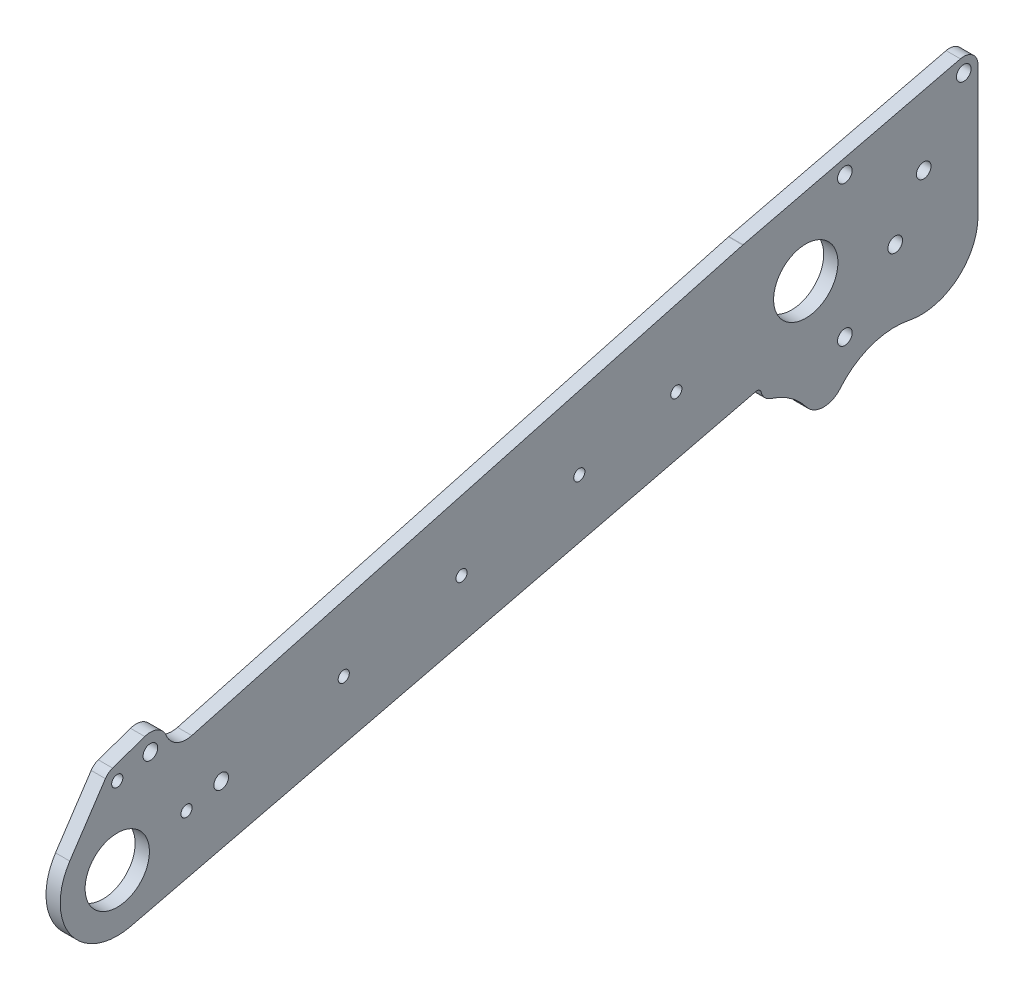
SolidWorks part; units mm, degrees
ref_plane "Alzado" through (0, 0, 0) normal (0, 0, 1) x (1, 0, 0)
ref_plane "Planta" through (0, 0, 0) normal (0, 1, 0) x (1, 0, 0)
ref_plane "Vista lateral" through (0, 0, 0) normal (1, 0, 0) x (0, 0, -1)
sketch "Croquis1" plane through (0, 0, 0) normal (0, 1, 0) x (1, 0, 0)
  line L1 (-101.6, -12.7) -> (101.6, -12.7)
  line L2 (-101.6, -12.7) -> (-101.6, 12.7)
  line L3 (-101.6, 12.7) -> (101.6, 12.7)
  line L4 (101.6, -12.7) -> (101.6, 12.7)
  line L5 (-101.6, -12.7) -> (101.6, 12.7) construction
  line L6 (-101.6, 12.7) -> (101.6, -12.7) construction
  point P0 (0, 0)
  dimension "D1" = 25.4
  dimension "D2" = 203.2
extrude "Saliente-Extruir1" add sketch "Croquis1" along normal blind 25.4
shell "Vaciado1" thickness 3.175 removed face at (-101.6, 12.7, 0) removed face at (101.6, 12.7, 0)
sketch "Croquis2" plane through (0, 25.4, 0) normal (0, 1, 0) x (1, 0, 0)
  line L0 (101.6, 12.7) -> (-101.6, 12.7) construction
  line L1 (-25.4, -12.7) -> (25.4, -12.7)
  line L2 (-25.4, -12.7) -> (-25.4, 12.7)
  line L3 (-25.4, 12.7) -> (25.4, 12.7)
  line L4 (25.4, -12.7) -> (25.4, 12.7)
  line L5 (-25.4, -12.7) -> (25.4, 12.7) construction
  line L6 (-25.4, 12.7) -> (25.4, -12.7) construction
  line L8 (-22.225, -9.525) -> (22.225, -9.525)
  line L9 (-22.225, -9.525) -> (-22.225, 9.525)
  line L10 (-22.225, 9.525) -> (22.225, 9.525)
  line L11 (22.225, -9.525) -> (22.225, 9.525)
  line L12 (-22.225, -9.525) -> (22.225, 9.525) construction
  line L13 (-22.225, 9.525) -> (22.225, -9.525) construction
  point P0 (0, 0)
  point P8 (0, 0)
  dimension "D1" = 50.8
  dimension "D2" = 3.175
  dimension "D3" = 3.175
extrude "Saliente-Extruir2" add sketch "Croquis2" along normal blind 247.65 separate body
sketch "Croquis3" plane through (0, 25.4, 0) normal (0, 1, 0) x (1, 0, 0)
  line L0 (0, 0) -> (0, 12.7) construction
  line L1 (25.4, 12.7) -> (-25.4, 12.7) construction
  circle A0 centre (-47.625, 0) radius 3.2639
  circle A1 centre (-79.375, 0) radius 3.2639
  circle A2 centre (79.375, 0) radius 3.2639
  circle A3 centre (47.625, 0) radius 3.2639
  dimension "D1" = 47.625
  dimension "D2" = 6.5278
  dimension "D3" = 31.75
extrude "Cortar-Extruir1" cut sketch "Croquis3" against normal through all
sketch "Croquis4" plane through (0, 0, 12.7) normal (0, 0, 1) x (1, 0, 0)
  line L0 (0, 25.4) -> (0, 139.6619) construction
  line L1 (-101.6, 25.4) -> (101.6, 25.4) construction
  line L2 (0, 139.6619) -> (-23.8125, 139.6619) construction
  circle A0 centre (0, 139.6619) radius 14.3129
  circle A1 centre (0, 139.6619) radius 23.8125 construction
  circle A2 centre (-23.8125, 139.6619) radius 2.4892 construction
  circle A3 centre (-11.9062, 160.2841) radius 2.4892
  circle A4 centre (11.9063, 160.2841) radius 2.4892
  circle A5 centre (23.8125, 139.6619) radius 2.4892 construction
  circle A6 centre (11.9062, 119.0397) radius 2.4892
  circle A7 centre (-11.9063, 119.0397) radius 2.4892
  dimension "D1" = 28.6258
  dimension "D3" = 47.625
  dimension "D4" = 4.9784
  dimension "D2" = 114.2619
  dimension "D6" = 23.8125
  dimension "D5" = 6
extrude "Cortar-Extruir2" cut sketch "Croquis4" against normal through all
sketch "Croquis8" plane through (0, 0, 12.7) normal (0, 0, 1) x (1, 0, 0)
  line L0 (0, 0) -> (0, 273.05) construction
  line L1 (-101.6, 12.7) -> (0, 12.7) construction
  line L2 (-101.6, 25.4) -> (-101.6, 0) construction
  line L3 (0, 12.7) -> (-12.7, 12.7) construction
  line L4 (0, 12.7) -> (12.7, 12.7) construction
  line L5 (-25.4, 273.05) -> (25.4, 273.05) construction
  line L6 (-12.7, 12.7) -> (-12.7, 25.4) construction
  circle A0 centre (0, 12.7) radius 2.4892
  circle A1 centre (-12.7, 12.7) radius 2.4892
  circle A2 centre (-25.4, 12.7) radius 2.4892
  circle A3 centre (-38.1, 12.7) radius 2.4892
  circle A4 centre (-50.8, 12.7) radius 2.4892
  circle A5 centre (0, 12.7) radius 2.4892
  circle A6 centre (-12.7, 12.7) radius 2.4892
  circle A7 centre (-25.4, 12.7) radius 2.4892
  circle A8 centre (-38.1, 12.7) radius 2.4892
  circle A9 centre (12.7, 12.7) radius 2.4892
  circle A10 centre (0, 12.7) radius 2.4892
  circle A11 centre (-12.7, 12.7) radius 2.4892
  circle A12 centre (-25.4, 12.7) radius 2.4892
  circle A13 centre (25.4, 12.7) radius 2.4892
  circle A14 centre (12.7, 12.7) radius 2.4892
  circle A15 centre (0, 12.7) radius 2.4892
  circle A16 centre (-12.7, 12.7) radius 2.4892
  circle A17 centre (38.1, 12.7) radius 2.4892
  circle A18 centre (25.4, 12.7) radius 2.4892
  circle A19 centre (12.7, 12.7) radius 2.4892
  circle A20 centre (0, 12.7) radius 2.4892
  circle A21 centre (12.7, 12.7) radius 2.4892
  circle A22 centre (25.4, 12.7) radius 2.4892
  circle A23 centre (38.1, 12.7) radius 2.4892
  circle A24 centre (50.8, 12.7) radius 2.4892
  circle A25 centre (-12.7, 25.4) radius 2.4892 [skipped]
  circle A26 centre (12.7, 25.4) radius 2.4892 [skipped]
  circle A27 centre (-12.7, 38.1) radius 2.4892
  circle A28 centre (12.7, 38.1) radius 2.4892
  circle A29 centre (-12.7, 50.8) radius 2.4892
  circle A30 centre (12.7, 50.8) radius 2.4892
  circle A31 centre (-12.7, 63.5) radius 2.4892
  circle A32 centre (12.7, 63.5) radius 2.4892
  circle A33 centre (-12.7, 76.2) radius 2.4892
  circle A34 centre (12.7, 76.2) radius 2.4892
  dimension "D1" = 4.9784
  dimension "D4" = 12.7
  dimension "D5" = 12.7
  dimension "D7" = 12.7
  dimension "D2" = 5
  dimension "D3" = 5
  dimension "D6" = 6
extrude "Cortar-Extruir4" cut sketch "Croquis8" against normal through all contours A4 | A3 | A2 | A1 | A0 | A9 | A13 | A17 | A24 | A28 | A29 | A30 | A31 | A32 | A34 | A33 | A27 region at (0, 12.7, 12.7) region at (-12.7, 12.7, 12.7) region at (-25.4, 12.7, 12.7) region at (-38.1, 12.7, 12.7) region at (-50.8, 12.7, 12.7) region at (12.7, 12.7, 12.7) region at (25.4, 12.7, 12.7) region at (38.1, 12.7, 12.7) region at (50.8, 12.7, 12.7) region at (12.7, 38.1, 12.7) region at (-12.7, 50.8, 12.7) region at (12.7, 50.8, 12.7) region at (-12.7, 63.5, 12.7) region at (12.7, 63.5, 12.7) region at (-12.7, 76.2, 12.7) region at (12.7, 76.2, 12.7)
sketch "Croquis6" plane through (0, 0, 12.7) normal (0, 0, 1) x (1, 0, 0)
  line L0 (25.4, 273.05) -> (25.4, 25.4) construction
  line L1 (-25.4, 88.646) -> (25.4, 88.646)
  line L2 (-25.4, 88.646) -> (-25.4, 114.046)
  line L3 (-25.4, 114.046) -> (25.4, 114.046)
  line L4 (25.4, 88.646) -> (25.4, 114.046)
  line L5 (-25.4, 88.646) -> (25.4, 114.046) construction
  line L6 (-25.4, 114.046) -> (25.4, 88.646) construction
  line L7 (-101.6, 25.4) -> (101.6, 25.4) construction
  line L9 (-22.225, 91.821) -> (22.225, 91.821)
  line L10 (-22.225, 91.821) -> (-22.225, 110.871)
  line L11 (-22.225, 110.871) -> (22.225, 110.871)
  line L12 (22.225, 91.821) -> (22.225, 110.871)
  line L13 (-22.225, 91.821) -> (22.225, 110.871) construction
  line L14 (-22.225, 110.871) -> (22.225, 91.821) construction
  point P0 (0, 101.346)
  point P11 (0, 101.346)
  dimension "D1" = 25.4
  dimension "D2" = 63.246
  dimension "D3" = 3.175
  dimension "D4" = 3.175
extrude "Saliente-Extruir3" add sketch "Croquis6" along normal blind 69.85 separate body
sketch "Croquis7" plane through (0, 114.046, 0) normal (0, 1, 0) x (1, 0, 0)
  line L0 (0, -12.7) -> (0, -82.55) construction
  line L1 (-25.4, -12.7) -> (25.4, -12.7) construction
  line L2 (25.4, -82.55) -> (-25.4, -82.55) construction
  line L3 (16.51, -12.7) -> (-16.51, -12.7)
  line L4 (25.4, -12.7) -> (-25.4, -12.7) construction
  line L5 (-16.51, -12.7) -> (-16.51, -34.798)
  line L6 (-13.208, -38.1) -> (13.208, -38.1)
  line L7 (16.51, -12.7) -> (16.51, -34.798)
  arc A0 (16.51, -34.798) -> (13.208, -38.1) centre (13.208, -34.798) cw
  arc A1 (-16.51, -34.798) -> (-13.208, -38.1) centre (-13.208, -34.798) ccw
  point P12 (0, -38.1)
  point P16 (16.51, -38.1)
  point P19 (-16.51, -38.1)
  dimension "D3" = 3.302
  dimension "D1" = 25.4
  dimension "D2" = 33.02
extrude "Cortar-Extruir3" cut sketch "Croquis7" against normal up to next (3.175 mm away)
sketch "Croquis11" plane through (25.4, 0, 0) normal (1, 0, 0) x (0, 0, -1)
  line L0 (0, -101.854) -> (-381, -101.854) construction
  line L1 (-82.55, 88.646) -> (-82.55, 114.046) construction
  line L2 (-82.55, 88.646) -> (-12.7, 88.646) construction
  line L6 (-517.96, -101.854) -> (-276.66, -101.854) construction
  line L7 (-517.96, -101.854) -> (-517.96, 139.446) construction
  line L8 (-517.96, 139.446) -> (-276.66, 139.446) construction
  line L9 (-276.66, -101.854) -> (-276.66, 139.446) construction
  circle A0 centre (-396.875, 145.796) radius 38.1
  dimension "D3" = 76.2
  dimension "D4" = 209.55
  dimension "D5" = 276.225
  dimension "D1" = 190.5
  dimension "D2" = 381
  dimension "D6" = 241.3
sketch "Croquis9" plane through (0, 0, 12.7) normal (0, 0, 1) x (1, 0, 0)
  line L0 (0, 0) -> (0, 273.05) construction
  line L1 (-25.4, 273.05) -> (25.4, 273.05) construction
  line L2 (50.8, 0) -> (-50.8, 0)
  line L3 (-101.6, 0) -> (101.6, 0) construction
  line L4 (-57.15, 6.35) -> (-57.15, 23.7481)
  line L5 (-101.6, 25.4) -> (101.6, 25.4) construction
  line L6 (-56.3451, 26.8425) -> (-27.2168, 79.0403)
  line L7 (-25.4, 273.05) -> (-25.4, 25.4) construction
  line L8 (-21.6717, 82.296) -> (21.6717, 82.296)
  line L9 (56.3451, 26.8425) -> (27.2168, 79.0403)
  line L10 (57.15, 6.35) -> (57.15, 23.7481)
  line L11 (-25.4, 88.646) -> (25.4, 88.646) construction
  circle A0 centre (-50.8, 12.7) radius 2.4892 construction
  arc A2 (-50.8, 0) -> (-57.15, 6.35) centre (-50.8, 6.35) cw
  arc A3 (-57.15, 23.7481) -> (-56.3451, 26.8425) centre (-50.8, 23.7481) cw
  arc A4 (-27.2168, 79.0403) -> (-21.6717, 82.296) centre (-21.6717, 75.946) cw
  arc A5 (27.2168, 79.0403) -> (21.6717, 82.296) centre (21.6717, 75.946) ccw
  arc A6 (57.15, 23.7481) -> (56.3451, 26.8425) centre (50.8, 23.7481) ccw
  arc A7 (50.8, 0) -> (57.15, 6.35) centre (50.8, 6.35) ccw
  circle A9 centre (-25.4, 12.7) radius 2.4892
  circle A10 centre (-25.4, 12.7) radius 2.4892
  circle A11 centre (-12.7, 12.7) radius 2.4892
  circle A12 centre (-12.7, 12.7) radius 2.4892
  circle A13 centre (0, 12.7) radius 2.4892
  circle A14 centre (0, 12.7) radius 2.4892
  circle A15 centre (0, 12.7) radius 2.4892
  circle A16 centre (0, 12.7) radius 2.4892
  circle A17 centre (12.7, 12.7) radius 2.4892
  circle A18 centre (12.7, 12.7) radius 2.4892
  circle A19 centre (-38.1, 12.7) radius 2.4892
  circle A20 centre (-38.1, 12.7) radius 2.4892
  circle A21 centre (-25.4, 12.7) radius 2.4892
  circle A22 centre (-25.4, 12.7) radius 2.4892
  circle A23 centre (-12.7, 12.7) radius 2.4892
  circle A24 centre (-12.7, 12.7) radius 2.4892
  circle A25 centre (0, 12.7) radius 2.4892
  circle A26 centre (0, 12.7) radius 2.4892
  circle A27 centre (-50.8, 12.7) radius 2.4892
  circle A28 centre (-50.8, 12.7) radius 2.4892
  circle A29 centre (-38.1, 12.7) radius 2.4892
  circle A30 centre (-38.1, 12.7) radius 2.4892
  circle A31 centre (25.4, 12.7) radius 2.4892
  circle A32 centre (25.4, 12.7) radius 2.4892
  circle A33 centre (38.1, 12.7) radius 2.4892
  circle A34 centre (38.1, 12.7) radius 2.4892
  circle A35 centre (-12.7, 12.7) radius 2.4892
  circle A36 centre (-12.7, 12.7) radius 2.4892
  circle A37 centre (0, 12.7) radius 2.4892
  circle A38 centre (0, 12.7) radius 2.4892
  circle A39 centre (12.7, 12.7) radius 2.4892
  circle A40 centre (12.7, 12.7) radius 2.4892
  circle A41 centre (25.4, 12.7) radius 2.4892
  circle A42 centre (25.4, 12.7) radius 2.4892
  circle A43 centre (-25.4, 12.7) radius 2.4892
  circle A44 centre (-25.4, 12.7) radius 2.4892
  circle A45 centre (-12.7, 12.7) radius 2.4892
  circle A46 centre (-12.7, 12.7) radius 2.4892
  circle A47 centre (50.8, 12.7) radius 2.4892
  circle A48 centre (50.8, 12.7) radius 2.4892
  circle A49 centre (38.1, 12.7) radius 2.4892
  circle A50 centre (38.1, 12.7) radius 2.4892
  circle A51 centre (25.4, 12.7) radius 2.4892
  circle A52 centre (25.4, 12.7) radius 2.4892
  circle A53 centre (12.7, 12.7) radius 2.4892
  circle A54 centre (12.7, 12.7) radius 2.4892
  circle A55 centre (0, 12.7) radius 2.4892
  circle A56 centre (0, 12.7) radius 2.4892
  circle A57 centre (12.7, 12.7) radius 2.4892
  circle A58 centre (12.7, 12.7) radius 2.4892
  circle A59 centre (-12.7, 76.2) radius 2.4892
  circle A60 centre (-12.7, 76.2) radius 2.4892
  circle A61 centre (12.7, 63.5) radius 2.4892
  circle A62 centre (12.7, 63.5) radius 2.4892
  circle A63 centre (-12.7, 63.5) radius 2.4892
  circle A64 centre (-12.7, 63.5) radius 2.4892
  circle A65 centre (12.7, 50.8) radius 2.4892
  circle A66 centre (12.7, 50.8) radius 2.4892
  circle A67 centre (-12.7, 50.8) radius 2.4892
  circle A68 centre (-12.7, 50.8) radius 2.4892
  circle A69 centre (12.7, 38.1) radius 2.4892
  circle A70 centre (12.7, 38.1) radius 2.4892
  circle A71 centre (-12.7, 38.1) radius 2.4892
  circle A72 centre (-12.7, 38.1) radius 2.4892
  circle A73 centre (12.7, 76.2) radius 2.4892
  circle A74 centre (12.7, 76.2) radius 2.4892
  point P22 (-57.15, 0)
  point P25 (-57.15, 25.4)
  point P28 (-25.4, 82.296)
  point P38 (0, 82.296)
  dimension "D1" = 6.35
  dimension "D3" = 6.35
  dimension "D37" = 6.35
  dimension "D4" = 0
  dimension "D5" = 0
  dimension "D6" = 0
  dimension "D7" = 0
  dimension "D8" = 0
  dimension "D9" = 0
  dimension "D10" = 0
  dimension "D11" = 0
  dimension "D12" = 0
  dimension "D13" = 0
  dimension "D14" = 0
  dimension "D15" = 0
  dimension "D16" = 0
  dimension "D17" = 0
  dimension "D18" = 0
  dimension "D19" = 0
  dimension "D20" = 0
  dimension "D21" = 0
  dimension "D22" = 0
  dimension "D23" = 0
  dimension "D24" = 0
  dimension "D25" = 0
  dimension "D26" = 0
  dimension "D27" = 0
  dimension "D28" = 0
  dimension "D29" = 0
  dimension "D30" = 0
  dimension "D31" = 0
  dimension "D32" = 0
  dimension "D33" = 0
  dimension "D34" = 0
  dimension "D35" = 0
  dimension "D36" = 0
extrude "Saliente-Extruir4" add sketch "Croquis9" along normal blind 6.35 separate body contours L0 L8 A4 L6 A3 A60 A64 A68 A72 | L0 A6 L9 A5 L8 A74 A70 A66 A62 | L0 A3 L4 A2 | L0 L2 A7 L10 A6 A56 region at (-24.3725, 36.0328, 12.7) region at (24.3725, 36.0328, 12.7)
sketch "Croquis15" plane through (25.4, 0, 0) normal (1, 0, 0) x (0, 0, -1)
  line L0 (-12.7, 0) -> (-12.7, 171.1325) construction
  line L1 (-12.7, 273.05) -> (-12.7, 25.4) construction
  line L2 (-72.5746, 227.1642) -> (-41.5317, 154.1315) construction
  line L3 (-105.4538, 208.2656) -> (-57.9713, 144.6822) construction
  line L4 (-94.6246, 238.2605) -> (-401.3483, 164.3633) construction
  line L5 (-392.4017, 127.2287) -> (-85.6779, 201.1258) construction
  line L8 (-82.55, 114.046) -> (-12.7, 114.046) construction
  circle A0 centre (-50.32, 150.396) radius 30
  arc A1 (-57.9713, 144.6822) -> (-41.5317, 154.1315) centre (-50.32, 150.396) ccw construction
  arc A2 (-401.3483, 164.3633) -> (-392.4017, 127.2287) centre (-396.875, 145.796) ccw construction
  arc A3 (-72.5746, 227.1642) -> (-105.4538, 208.2656) centre (-90.1513, 219.6932) ccw construction
  arc A4 (-85.6779, 201.1258) -> (-94.6246, 238.2605) centre (-90.1513, 219.6932) ccw construction
  dimension "D2" = 60
  dimension "D3" = 19.0986
  dimension "D4" = 38.1972
  dimension "D1" = 171.1325
  dimension "D7" = 6.35
  dimension "D8" = 7.62
sketch "Croquis16" plane through (25.4, 0, 0) normal (1, 0, 0) x (0, 0, -1)
  line L0 (-50.32, 150.396) -> (-50.32, 175.796) construction
  line L1 (-13.4332, 272.8734) -> (-118.1525, 247.644)
  line L2 (-82.55, 94.996) -> (-82.55, 113.9625)
  line L3 (-82.5522, 114.1295) -> (-83.4835, 149.5234)
  line L4 (-76.2, 88.646) -> (6.35, 88.646)
  line L5 (12.7, 273.05) -> (12.7, 25.4) construction
  line L6 (12.7, 94.996) -> (12.7, 266.7)
  line L7 (6.35, 273.05) -> (-11.9459, 273.05)
  line L8 (-94.6246, 238.2605) -> (-401.3483, 164.3633) construction
  line L9 (-122.8385, 239.9833) -> (-110.0117, 186.743)
  line L10 (-90.1513, 219.6932) -> (-116.4251, 213.3632) construction
  circle A0 centre (-90.1513, 219.6932) radius 14.3256
  circle A1 centre (-50.32, 150.396) radius 33.175
  circle A4 centre (-50.32, 150.396) radius 9.5631
  circle A5 centre (-50.32, 150.396) radius 25.4 construction
  circle A6 centre (-50.32, 175.796) radius 2.4892
  circle A7 centre (-32.3595, 168.3565) radius 2.4892 construction
  circle A8 centre (-24.92, 150.396) radius 2.4892
  circle A9 centre (-32.3595, 132.4355) radius 2.4892
  circle A10 centre (-50.32, 124.996) radius 2.4892
  circle A11 centre (-68.2805, 132.4355) radius 2.4892
  circle A12 centre (-75.72, 150.396) radius 2.4892
  circle A13 centre (-68.2805, 168.3565) radius 2.4892
  arc A18 (-105.7366, 182.1707) -> (-83.4864, 151.1506) centre (-115.2282, 151.8727) cw
  arc A19 (-110.0117, 186.743) -> (-105.7366, 182.1707) centre (-103.8383, 188.2304) ccw
  arc A21 (-118.1525, 247.644) -> (-122.8385, 239.9833) centre (-116.6652, 241.4706) ccw
  arc A23 (-11.9459, 273.05) -> (-13.4332, 272.8734) centre (-11.9459, 266.7) ccw
  circle A26 centre (-50.32, 150.396) radius 30 construction
  arc A29 (-82.55, 113.9625) -> (-82.5522, 114.1295) centre (-88.9, 113.9625) ccw
  arc A31 (12.7, 266.7) -> (6.35, 273.05) centre (6.35, 266.7) ccw
  arc A32 (6.35, 88.646) -> (12.7, 94.996) centre (6.35, 94.996) ccw
  arc A33 (-82.55, 94.996) -> (-76.2, 88.646) centre (-76.2, 94.996) ccw
  point P45 (-12.7, 273.05)
  point P72 (-82.55, 114.046)
  point P74 (12.7, 273.05)
  point P77 (12.7, 88.646)
  point P80 (-82.55, 88.646)
  dimension "D1" = 28.6512
  dimension "D2" = 3.175
  dimension "D3" = 31.75
  dimension "D4" = 19.1262
  dimension "D5" = 50.8
  dimension "D6" = 4.9784
  dimension "D9" = 6.35
  dimension "D10" = 6.35
  dimension "D14" = 6.35
  dimension "D15" = 6.35
  dimension "D12" = 6.35
  dimension "D8" = 25.4
  dimension "D11" = 12.7
  dimension "D7" = 8
extrude "Saliente-Extruir5" add sketch "Croquis16" along normal blind 6.35 separate body contours L4 A32 A31 A23 | L2 A33 L4 A23 L1 A21 L9 A19 A18 A1 L3 A29 A0 | A1 A13 A12 A11 A10 A9 A8 A6 A4 region at (25.4, 188.5949, 38.9873) region at (25.4, 182.6306, 49.9534)
sketch "Croquis12" plane through (25.4, 0, 0) normal (1, 0, 0) x (0, 0, -1)
  line L0 (-82.55, 101.346) -> (-12.7, 101.346) construction
  line L1 (-82.55, 88.646) -> (-82.55, 114.046) construction
  line L2 (-12.7, 88.646) -> (-12.7, 114.046) construction
  line L3 (0, 273.05) -> (0, 0) construction
  line L4 (-12.7, 273.05) -> (12.7, 273.05) construction
  line L5 (0, 101.346) -> (-12.7, 101.346) construction
  line L6 (0, 101.346) -> (0, 114.046) construction
  circle A1 centre (0, 101.346) radius 2.4892
  circle A2 centre (-12.7, 101.346) radius 2.4892 [skipped]
  circle A3 centre (-25.4, 101.346) radius 2.4892
  circle A4 centre (-38.1, 101.346) radius 2.4892
  circle A5 centre (-50.8, 101.346) radius 2.4892
  circle A6 centre (0, 114.046) radius 2.4892
  circle A7 centre (0, 126.746) radius 2.4892
  circle A8 centre (0, 139.446) radius 2.4892
  circle A9 centre (0, 152.146) radius 2.4892
  circle A10 centre (0, 164.846) radius 2.4892
  circle A11 centre (0, 177.546) radius 2.4892
  circle A12 centre (0, 190.246) radius 2.4892
  circle A13 centre (0, 202.946) radius 2.4892
  circle A14 centre (0, 215.646) radius 2.4892
  circle A15 centre (0, 228.346) radius 2.4892
  circle A16 centre (0, 241.046) radius 2.4892
  circle A17 centre (0, 253.746) radius 2.4892
  circle A18 centre (0, 266.446) radius 2.4892
  circle A19 centre (-63.5, 101.346) radius 2.4892
  circle A20 centre (-76.2, 101.346) radius 2.4892
  dimension "D1" = 4.9784
  dimension "D3" = 12.7
  dimension "D5" = 12.7
  dimension "D2" = 7
  dimension "D4" = 14
extrude "Cortar-Extruir5" cut sketch "Croquis12" against normal through all and the other way through all
sketch "Croquis17" plane through (31.75, 0, 0) normal (1, 0, 0) x (0, 0, -1)
  line L0 (-403.5186, 170.3118) -> (-118.2389, 247.6205)
  line L1 (-118.0654, 247.6649) -> (-21.2705, 270.9852)
  line L2 (-390.9258, 121.1026) -> (-118.1525, 186.8202)
  line L3 (-392.4017, 127.2287) -> (-85.6779, 201.1258) construction
  line L4 (-118.1525, 186.8202) -> (-112.4025, 188.2055)
  line L5 (-13.4332, 206.3797) -> (-13.4332, 264.8118)
  line L6 (-398.9636, 186.2074) -> (-384.6217, 191.2027)
  line L7 (-402.1634, 183.7258) -> (-418.0287, 159.8559)
  circle A0 centre (-396.875, 145.796) radius 14.3256
  circle A1 centre (-90.1513, 219.6932) radius 14.3256
  circle A2 centre (-396.875, 145.796) radius 25.4
  arc A3 (-118.2389, 247.6205) -> (-118.0654, 247.6649) centre (-116.578, 241.4916) cw
  arc A4 (-21.2705, 270.9852) -> (-13.4332, 264.8118) centre (-19.7832, 264.8118) cw
  arc A5 (-13.4332, 206.3797) -> (-43.9384, 181.4981) centre (-38.8332, 206.3797) cw
  circle A6 centre (-50.32, 150.396) radius 31.75
  arc A8 (-110.0117, 186.743) -> (-105.7366, 182.1707) centre (-103.8383, 188.2304) ccw construction
  arc A9 (-110.0117, 186.743) -> (-105.7366, 182.1707) centre (-103.8383, 188.2304) ccw
  arc A10 (-110.0117, 186.743) -> (-112.4025, 188.2055) centre (-111.9383, 186.2789) ccw
  arc A11 (-83.4864, 151.1506) -> (-105.7366, 182.1707) centre (-115.2282, 151.8727) ccw construction
  arc A12 (-89.8175, 170.9084) -> (-105.7366, 182.1707) centre (-115.2282, 151.8727) ccw
  arc A13 (-89.8175, 170.9084) -> (-74.8387, 170.5677) centre (-82.1943, 176.6192) ccw
  circle A14 centre (-396.875, 180.2108) radius 6.35
  circle A15 centre (-382.1153, 184.0067) radius 7.62
  arc A17 (-375.0276, 186.8047) -> (-363.6766, 181.1087) centre (-366.1679, 190.3021) ccw
  point P19 (-118.1525, 247.644)
  point P23 (-13.4332, 272.8734)
  line M28 (-13.4332, 272.8734) -> (-118.1525, 247.644)
  arc M29 (-118.1525, 247.644) -> (-122.8385, 239.9833) centre (-116.6652, 241.4706) ccw
  line M30 (-122.8385, 239.9833) -> (-110.0117, 186.743)
  circle M38 centre (-90.1513, 219.6932) radius 14.3256
  dimension "D1" = 28.6512
  dimension "D2" = 50.8
  dimension "D3" = 6.35
  dimension "D4" = 63.5
  dimension "D5" = 9.525
  dimension "D6" = 25.4
  dimension "D7" = 12.7
  dimension "D8" = 34.4148
  dimension "D9" = 15.24
  dimension "D10" = 15.24
  dimension "D11" = 9.525
extrude "Saliente-Extruir6" add sketch "Croquis17" along normal blind 6.35 separate body contours A2 L2 L0 M30 M29 | L5 A4 A3 L0 M28 M29 M30 M38 | A2 A0 | A14 L7 A2 L0 | A14 | A15 | A17 A15 L0 region at (31.75, 166.8023, 412.0119) region at (31.75, 184.8147, 244.5216) region at (31.75, 165.3985, 381.8776) region at (31.75, 180.6264, 372.6967) region at (31.75, 184.0067, 382.1153) region at (31.75, 180.2108, 396.875) region at (31.75, 220.7032, 61.6214)
sketch "Croquis18" plane through (38.1, 0, 0) normal (1, 0, 0) x (0, 0, -1)
  line L0 (-122.8385, 239.9833) -> (-110.0117, 186.743) construction
  line L1 (-122.754, 239.6323) -> (-111.9631, 194.8431)
  line L2 (-403.5186, 170.3118) -> (-118.2389, 247.6205) construction
  line L3 (-402.1634, 183.7258) -> (-418.0287, 159.8559) construction
  line L4 (-398.9636, 186.2074) -> (-384.6217, 191.2027) construction
  line L5 (-402.1634, 183.7258) -> (-418.0287, 159.8559)
  line L6 (-390.9258, 121.1026) -> (-118.1525, 186.8202) construction
  line L7 (-403.5186, 170.3118) -> (-130.5882, 244.274)
  line L8 (-398.9636, 186.2074) -> (-384.6217, 191.2027)
  line L10 (-122.8385, 239.9833) -> (-110.0117, 186.743) construction
  line L11 (-390.9258, 121.1026) -> (-116.6492, 187.1824)
  circle A1 centre (-396.875, 145.796) radius 25.4
  circle A2 centre (-396.875, 145.796) radius 25.4
  arc A3 (-116.6492, 187.1824) -> (-111.9631, 194.8431) centre (-118.1365, 193.3558) ccw
  circle A5 centre (-396.875, 145.796) radius 14.3256
  circle A6 centre (-396.875, 145.796) radius 14.3256
  arc A12 (-122.754, 239.6323) -> (-130.5882, 244.274) centre (-128.9273, 238.145) ccw
  circle A14 centre (-396.875, 180.2108) radius 6.35 construction
  arc A15 (-375.0276, 186.8047) -> (-363.6766, 181.1087) centre (-366.1679, 190.3021) ccw construction
  circle A16 centre (-396.875, 180.2108) radius 6.35
  arc A17 (-375.0276, 186.8047) -> (-384.6217, 191.2027) centre (-382.1153, 184.0067) ccw construction
  arc A18 (-375.0276, 186.8047) -> (-363.6766, 181.1087) centre (-366.1679, 190.3021) ccw
  arc A19 (-375.0276, 186.8047) -> (-384.6217, 191.2027) centre (-382.1153, 184.0067) ccw
  point P18 (-110.4758, 188.6697)
  line M10 (-118.2389, 247.6205) -> (-363.6766, 181.1087)
  arc M11 (-418.0287, 159.8559) -> (-390.9258, 121.1026) centre (-396.875, 145.796) ccw
  circle M13 centre (-396.875, 145.796) radius 14.3256
  line M33 (-402.1634, 183.7258) -> (-418.0287, 159.8559)
  arc M35 (-398.9636, 186.2074) -> (-402.1634, 183.7258) centre (-396.875, 180.2108) ccw
  dimension "D2" = 6.35
  dimension "D1" = 0
  dimension "D3" = 0
extrude "Saliente-Extruir7" add sketch "Croquis18" along normal blind 6.35 from surface separate body contours L1 A12 A2 A3 M10 | A2 M11 M13 | A16 A2 L7 M33 | A16 M35 region at (38.1, 184.7417, 244.7476) region at (38.1, 180.3032, 388.6206) region at (38.1, 131.6506, 417.1009) region at (38.1, 180.2108, 396.875) starting at face at (25.4, 101.346, -2.4892)
sketch "Croquis22" plane through (38.1, 0, 0) normal (1, 0, 0) x (0, 0, -1)
  line L0 (-396.875, 145.796) -> (-90.1513, 219.6932) construction
  line L1 (-90.1513, 219.6932) -> (-50.32, 150.396) construction
  line L4 (-50.32, 236.121) -> (-37.62, 236.121) construction
  line L5 (-21.2705, 270.9852) -> (-118.0654, 247.6649) construction
  circle A0 centre (-396.875, 180.2108) radius 2.4892
  circle A1 centre (-350.5748, 156.9508) radius 3.2639
  circle A2 centre (-396.875, 145.796) radius 19.0986 construction
  arc A3 (-401.3483, 164.3633) -> (-392.4017, 127.2287) centre (-396.875, 145.796) ccw construction
  circle A4 centre (-350.5748, 156.9508) radius 6.35 construction
  circle A7 centre (-72.747, 189.4137) radius 3.2639
  circle A8 centre (-72.747, 189.4137) radius 6.35 construction
  circle A9 centre (-50.32, 213.896) radius 6.35 construction
  circle A10 centre (-50.32, 213.896) radius 3.2639
  circle A13 centre (-37.62, 236.121) radius 3.2639
  circle A14 centre (-37.62, 236.121) radius 6.35 construction
  circle A15 centre (-72.747, 252.0515) radius 3.2639
  circle A16 centre (-72.747, 252.0515) radius 6.35 construction
  circle A17 centre (-19.7832, 264.8118) radius 6.35 construction
  circle A18 centre (-19.7832, 264.8118) radius 3.2639
  circle A19 centre (-382.1153, 184.0067) radius 3.2639
  circle A20 centre (-366.0082, 153.2326) radius 2.4892
  circle A21 centre (-366.0082, 153.2326) radius 4.7625 construction
  dimension "D1" = 6.5278
  dimension "D2" = 47.625
  dimension "D3" = 12.7
  dimension "D4" = 34.925
  dimension "D5" = 63.5
  dimension "D6" = 22.225
  dimension "D7" = 12.7
  dimension "D8" = 4.9784
  dimension "D9" = 6.5278
  dimension "D10" = 9.525
  dimension "D11" = 31.75
extrude "Cortar-Extruir6" cut sketch "Croquis22" against normal through all
sketch "Croquis24" plane through (38.1, 0, 0) normal (1, 0, 0) x (0, 0, -1)
  line L0 (-396.875, 145.796) -> (-90.1513, 219.6932) construction
  line L1 (-243.5131, 182.7446) -> (-247.9864, 201.3119) construction
  line L2 (-94.6246, 238.2605) -> (-401.3483, 164.3633) construction
  circle A0 centre (-295.9867, 170.1024) radius 2.4892
  circle A1 centre (-191.0395, 195.3867) radius 2.4892
  circle A2 centre (-243.5131, 182.7446) radius 2.4892
  circle A3 centre (-147.826, 205.7979) radius 2.4892
  dimension "D1" = 4.9784
  dimension "D2" = 53.975
  dimension "D3" = 44.45
sketch "Croquis25" plane through (31.75, 0, 0) normal (1, 0, 0) x (0, 0, -1)
  line L0 (-12.7, 0) -> (-12.7, 139.7) construction
  line L1 (-12.7, 123.825) -> (-12.7, 155.575)
  line L2 (-12.7, 0) -> (-12.7, 171.1325) construction
  line L3 (-15.875, 158.75) -> (-17.145, 158.75)
  line L4 (-20.32, 155.575) -> (-20.32, 123.825)
  line L5 (-12.7, 139.7) -> (-20.32, 139.7) construction
  line L6 (-15.875, 120.65) -> (-17.145, 120.65)
  arc A0 (-12.7, 155.575) -> (-15.875, 158.75) centre (-15.875, 155.575) ccw
  arc A1 (-15.875, 120.65) -> (-12.7, 123.825) centre (-15.875, 123.825) ccw
  arc A2 (-17.145, 120.65) -> (-20.32, 123.825) centre (-17.145, 123.825) cw
  arc A3 (-17.145, 158.75) -> (-20.32, 155.575) centre (-17.145, 155.575) ccw
  point P13 (-12.7, 158.75)
  point P16 (-12.7, 120.65)
  point P19 (-20.32, 120.65)
  point P22 (-20.32, 158.75)
  dimension "D4" = 3.175
  dimension "D1" = 139.7
  dimension "D2" = 7.62
  dimension "D3" = 38.1
extrude "Cortar-Extruir8" cut sketch "Croquis25" against normal through all
extrude "Cortar-Extruir9" cut sketch "Croquis24" against normal through all
delete or keep bodies "Sólido-Eliminar/Conservar 1" [suppressed] type keep bodies bodies 112
delete or keep bodies "Sólido-Eliminar/Conservar 2" [suppressed] type keep bodies bodies 111
delete or keep bodies "Sólido-Eliminar/Conservar 3" [suppressed] type keep bodies bodies 107
delete or keep bodies "Sólido-Eliminar/Conservar 4" [suppressed] type keep bodies bodies 109
delete or keep bodies "Sólido-Eliminar/Conservar 5" [suppressed] type keep bodies bodies 121
delete or keep bodies "Sólido-Eliminar/Conservar 6" [suppressed] type keep bodies bodies 125
sketch "Croquis29" [suppressed] plane through (0, 0, 0) normal (1, 0, 0) x (0, 0, -1)
  line L0 (-392.4017, 127.2287) -> (-85.6779, 201.1258) construction
  line L1 (-94.6246, 238.2605) -> (-401.3483, 164.3633) construction
  line L2 (-392.4017, 127.2287) -> (-85.6779, 201.1258) construction
  line L3 (-94.6246, 238.2605) -> (-401.3483, 164.3633) construction
  line L4 (-392.8842, 129.2314) -> (-86.1604, 203.1285)
  line L5 (-94.1421, 236.2578) -> (-400.8658, 162.3606)
  line L6 (-391.9941, 125.5371) -> (-85.2704, 199.4342)
  line L7 (-95.0321, 239.9521) -> (-401.7559, 166.0549)
  arc A0 (-85.6779, 201.1258) -> (-94.6246, 238.2605) centre (-90.1513, 219.6932) ccw construction
  arc A1 (-401.3483, 164.3633) -> (-392.4017, 127.2287) centre (-396.875, 145.796) ccw construction
  arc A2 (-85.6779, 201.1258) -> (-94.6246, 238.2605) centre (-90.1513, 219.6932) ccw construction
  arc A3 (-401.3483, 164.3633) -> (-392.4017, 127.2287) centre (-396.875, 145.796) ccw construction
  arc A4 (-86.1604, 203.1285) -> (-94.1421, 236.2578) centre (-90.1513, 219.6932) ccw
  arc A5 (-400.8658, 162.3606) -> (-392.8842, 129.2314) centre (-396.875, 145.796) ccw
  arc A6 (-401.7559, 166.0549) -> (-391.9941, 125.5371) centre (-396.875, 145.796) ccw
  arc A7 (-85.2704, 199.4342) -> (-95.0321, 239.9521) centre (-90.1513, 219.6932) ccw
  dimension "D1" = 2.06
  dimension "D2" = 3.8
extrude "Saliente-Extruir9" [suppressed] add sketch "Croquis29" along normal mid plane 9 separate body
sketch "Croquis30" [suppressed] plane through (0, 0, 0) normal (1, 0, 0) x (0, 0, -1)
  line L0 (-72.5746, 227.1642) -> (-41.5317, 154.1315) construction
  line L1 (-105.4538, 208.2656) -> (-57.9713, 144.6822) construction
  line L2 (-72.5746, 227.1642) -> (-41.5317, 154.1315) construction
  line L3 (-105.4538, 208.2656) -> (-57.9713, 144.6822) construction
  line L4 (-74.4704, 226.3584) -> (-43.4275, 153.3257)
  line L5 (-103.8032, 209.4982) -> (-56.3207, 145.9148)
  line L6 (-106.8479, 207.2245) -> (-59.3654, 143.6411)
  line L7 (-70.9732, 227.8449) -> (-39.9303, 154.8122)
  arc A0 (-57.9713, 144.6822) -> (-41.5317, 154.1315) centre (-50.32, 150.396) ccw construction
  arc A1 (-72.5746, 227.1642) -> (-105.4538, 208.2656) centre (-90.1513, 219.6932) ccw construction
  arc A2 (-57.9713, 144.6822) -> (-41.5317, 154.1315) centre (-50.32, 150.396) ccw construction
  arc A3 (-72.5746, 227.1642) -> (-105.4538, 208.2656) centre (-90.1513, 219.6932) ccw construction
  arc A4 (-56.3207, 145.9148) -> (-43.4275, 153.3257) centre (-50.32, 150.396) ccw
  arc A5 (-74.4704, 226.3584) -> (-103.8032, 209.4982) centre (-90.1513, 219.6932) ccw
  arc A6 (-70.9732, 227.8449) -> (-106.8479, 207.2245) centre (-90.1513, 219.6932) ccw
  arc A7 (-59.3654, 143.6411) -> (-39.9303, 154.8122) centre (-50.32, 150.396) ccw
  dimension "D1" = 2.06
  dimension "D2" = 3.8
extrude "Saliente-Extruir10" [suppressed] add sketch "Croquis30" along normal mid plane 15 separate body
delete or keep bodies "Sólido-Eliminar/Conservar 7" [suppressed] type keep bodies bodies 123
delete or keep bodies "Sólido-Eliminar/Conservar 8" [suppressed] type keep bodies bodies 124
sketch "Croquis31" [suppressed] plane through (31.75, 0, 0) normal (1, 0, 0) x (0, 0, -1)
  line L0 (-402.1634, 183.7258) -> (-418.0287, 159.8559) construction
  line L1 (-402.1634, 183.7258) -> (-418.0287, 159.8559)
  line L2 (-361.1143, 149.1863) -> (-377.2995, 129.6108)
  circle A0 centre (-396.875, 180.2108) radius 6.35
  circle A1 centre (-366.0082, 153.2326) radius 6.35
  circle A2 centre (-350.5748, 156.9508) radius 6.35 construction
  arc A3 (-398.9636, 186.2074) -> (-402.1634, 183.7258) centre (-396.875, 180.2108) ccw construction
  circle A4 centre (-396.875, 145.796) radius 25.4
  arc A5 (-418.0287, 159.8559) -> (-390.9258, 121.1026) centre (-396.875, 145.796) ccw construction
  circle A7 centre (-396.875, 145.796) radius 17.4625
  circle A8 centre (-382.1153, 184.0067) radius 7.62 construction
  arc A9 (-375.0276, 186.8047) -> (-384.6217, 191.2027) centre (-382.1153, 184.0067) ccw construction
  arc A10 (-391.2071, 183.0739) -> (-363.9295, 159.2327) centre (-348.1311, 204.8335) ccw
  dimension "D1" = 12.7
  dimension "D2" = 34.925
  dimension "D3" = 48.26
extrude "Saliente-Extruir11" [suppressed] add sketch "Croquis31" along normal blind 1.5875 separate body
delete or keep bodies "Sólido-Eliminar/Conservar 9" [suppressed] type keep bodies bodies 126
delete or keep bodies "Sólido-Eliminar/Conservar 10" [suppressed] type keep bodies bodies 127
delete or keep bodies "Sólido-Eliminar/Conservar 11" type keep bodies bodies 125
equation "\"D1@Croquis15\"=5.5500+1.1875pulgadas"
equation "\"D3@Croquis15\"=(12*5mm)/pi"
equation "\"D4@Croquis15\"=(24*5mm)/pi"
equation "\"D5@Croquis15\"=(50*5mm)+1mm"
equation "\"D6@Croquis15\"=(150*5mm)+1mm"
